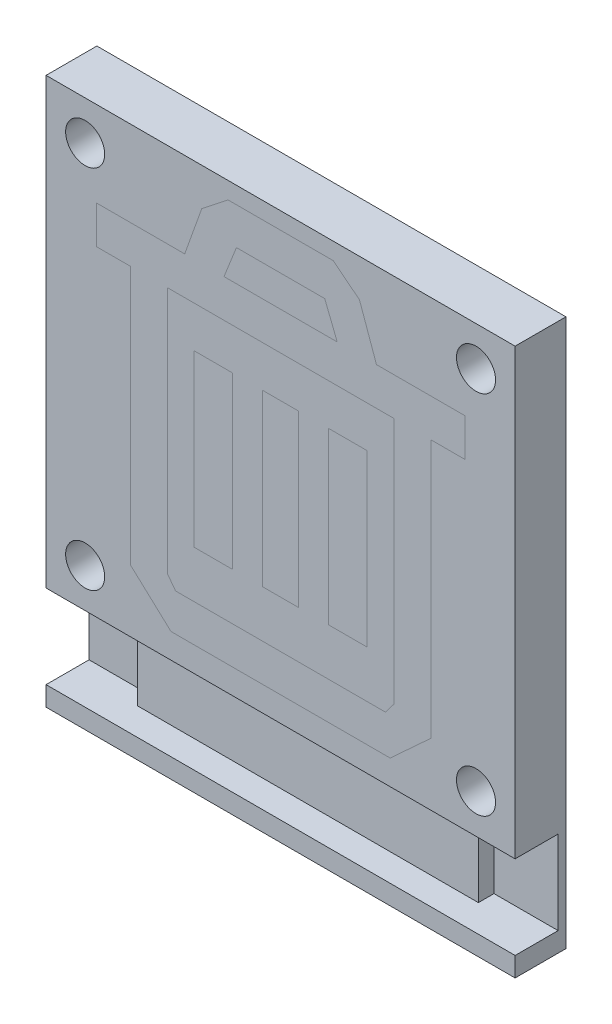
SolidWorks part; units mm, degrees
ref_plane "Front Plane" through (0, 0, 0) normal (0, 0, 1) x (1, 0, 0)
ref_plane "Top Plane" through (0, 0, 0) normal (0, 1, 0) x (1, 0, 0)
ref_plane "Right Plane" through (0, 0, 0) normal (1, 0, 0) x (0, 0, -1)
sketch "Sketch1" plane through (0, 0, 0) normal (0, 0, 1) x (1, 0, 0)
  line L0 (137.9686, 390.3403) -> (878.5926, 390.3403) construction
  line L1 (-39.205, 61.8798) -> (20.795, 61.8798)
  line L2 (-39.205, 61.8798) -> (-39.205, -8.1202)
  line L3 (-39.205, -8.1202) -> (20.795, -8.1202)
  line L4 (20.795, 61.8798) -> (20.795, -8.1202)
  line L5 (-9.205, -8.1202) -> (-9.205, 61.8798) construction
  line L6 (-9.205, 5.0798) -> (-9.205, -5.6202) construction
  line L7 (16.595, 5.0798) -> (-35.005, 5.0798)
  line L8 (16.595, 5.0798) -> (16.595, -5.6202)
  line L9 (16.595, -5.6202) -> (-35.005, -5.6202)
  line L10 (-35.005, 5.0798) -> (-35.005, -5.6202)
  line L11 (-2.4787, 59.7179) -> (-15.9313, 59.7179)
  line L12 (-35.005, -5.6202) -> (-31.005, -5.6202)
  line L13 (-35.005, -5.6202) -> (-35.005, 5.0798)
  line L14 (-35.005, 5.0798) -> (-31.005, 5.0798)
  line L15 (-31.005, -5.6202) -> (-31.005, 5.0798)
  line L16 (16.595, -5.6202) -> (12.595, -5.6202)
  line L17 (16.595, -5.6202) -> (16.595, 5.0798)
  line L18 (16.595, 5.0798) -> (12.595, 5.0798)
  line L19 (12.595, -5.6202) -> (12.595, 5.0798)
  line L20 (-35.005, 5.0798) -> (-39.205, 5.0798)
  line L21 (-35.005, 5.0798) -> (-35.005, -5.6202)
  line L22 (-35.005, -5.6202) -> (-39.205, -5.6202)
  line L23 (-39.205, 5.0798) -> (-39.205, -5.6202)
  line L24 (16.595, 5.0798) -> (20.795, 5.0798)
  line L25 (16.595, 5.0798) -> (16.595, -5.6202)
  line L26 (16.595, -5.6202) -> (20.795, -5.6202)
  line L27 (20.795, 5.0798) -> (20.795, -5.6202)
  line L28 (-15.9313, 59.7179) -> (-19.2931, 57.063)
  line L29 (-19.2931, 57.063) -> (-21.4699, 50.9645)
  line L30 (-21.4699, 50.9645) -> (-32.7735, 50.9645)
  line L31 (-32.7735, 50.9645) -> (-32.7735, 46.12)
  line L32 (-32.7735, 46.12) -> (-28.4218, 46.12)
  line L33 (-28.4218, 46.12) -> (-28.4218, 13.0402)
  line L34 (-28.4218, 13.0402) -> (-23.2226, 8.2562)
  line L35 (-23.2226, 8.2562) -> (4.8126, 8.2562)
  line L36 (4.2315, 13.0402) -> (-22.6415, 13.0402)
  line L37 (-22.6415, 13.0402) -> (-23.6864, 14.4507)
  line L38 (-23.6864, 14.4507) -> (-23.6864, 46.12)
  line L39 (-23.6864, 46.12) -> (5.2763, 46.12)
  line L40 (-1.9643, 50.9645) -> (-16.4457, 50.9645)
  line L41 (-16.4457, 50.9645) -> (-14.8536, 54.9715)
  line L42 (-14.8536, 54.9715) -> (-3.5564, 54.9715)
  line L43 (-6.911, 40.837) -> (-11.499, 40.837)
  line L44 (-11.499, 40.837) -> (-11.499, 19.0717)
  line L45 (-11.499, 19.0717) -> (-6.911, 19.0717)
  line L46 (-20.278, 40.837) -> (-15.3428, 40.837)
  line L47 (-15.3428, 40.837) -> (-15.3428, 19.0717)
  line L48 (-15.3428, 19.0717) -> (-20.278, 19.0717)
  line L49 (-20.278, 19.0717) -> (-20.278, 40.837)
  line L50 (1.868, 19.0717) -> (1.868, 40.837)
  line L51 (-3.0672, 19.0717) -> (1.868, 19.0717)
  line L52 (-3.0672, 40.837) -> (-3.0672, 19.0717)
  line L53 (1.868, 40.837) -> (-3.0672, 40.837)
  line L54 (-6.911, 40.837) -> (-6.911, 19.0717)
  line L55 (-1.9643, 50.9645) -> (-3.5564, 54.9715)
  line L56 (5.2763, 14.4507) -> (5.2763, 46.12)
  line L57 (4.2315, 13.0402) -> (5.2763, 14.4507)
  line L58 (10.0118, 13.0402) -> (4.8126, 8.2562)
  line L59 (10.0118, 46.12) -> (10.0118, 13.0402)
  line L60 (14.3635, 46.12) -> (10.0118, 46.12)
  line L61 (14.3635, 50.9645) -> (14.3635, 46.12)
  line L62 (3.0599, 50.9645) -> (14.3635, 50.9645)
  line L63 (0.8831, 57.063) -> (3.0599, 50.9645)
  line L64 (-2.4787, 59.7179) -> (0.8831, 57.063)
  point P34 (-9.205, 59.7179)
  point P35 (-9.205, 54.9715)
  point P36 (-9.205, 50.9645)
  point P37 (-9.205, 40.837)
  point P38 (-9.205, 46.12)
  point P39 (-9.205, 19.0717)
  point P40 (-9.205, 8.2562)
  point P41 (-9.205, 13.0402)
  dimension "D1" = 70
  dimension "D2" = 60
  dimension "D3" = 10.7
  dimension "D5" = 2.5
  dimension "D6" = 4
  dimension "D7" = 4
extrude "Back Plate" add sketch "Sketch1" along normal blind 1 contours L7 L24 L4 L1 L2 L20 | L9 L19 L7 L15 | L9 L15 L7 L10 | L22 L10 L20 L2 | L26 L9 L22 L2 L3 L4 | L19 L9 L8 L7 | L8 L26 L4 L24 | L36 L57 L56 L39 L38 L37 L43 L54 L45 L44 L48 L49 L46 L47 L53 L50 L51 L52 | L40 L55 L42 L41 region at (-9.205, 61.0536, 0) region at (-37.105, -0.2702, 0) region at (18.695, -0.2702, 0) region at (-9.205, -6.8702, 0) region at (-33.005, -0.2702, 0) region at (14.595, -0.2702, 0) region at (-9.205, -0.2702, 0) region at (-9.205, 13.4799, 0) region at (-9.205, 52.8855, 0)
extrude "Neopixel Back" add sketch "Sketch1<4>" along normal blind 3 contours L9 L19 L7 L15 region at (-9.205, -0.2702, 0)
sketch "Sketch1<4>" plane through (0, 0, 0) normal (0, 0, 1) x (1, 0, 0) same geometry as "Sketch1"
extrude "Main Color" add sketch "Sketch1<5>" along normal blind 6.5 contours L7 L24 L4 L1 L2 L20 | L26 L9 L22 L2 L3 L4 | L36 L57 L56 L39 L38 L37 L43 L54 L45 L44 L48 L49 L46 L47 L53 L50 L51 L52 | L40 L55 L42 L41 region at (-9.205, 61.0536, 0) region at (-9.205, -6.8702, 0) region at (-9.205, 13.4799, 0) region at (-9.205, 52.8855, 0)
sketch "Sketch1<5>" plane through (0, 0, 0) normal (0, 0, 1) x (1, 0, 0) same geometry as "Sketch1"
sketch "Sketch2" plane through (0, 0, 6.5) normal (0, 0, 1) x (1, 0, 0)
  line L0 (-9.205, 61.8798) -> (-9.205, 5.0798) construction
  line L1 (-39.205, 61.8798) -> (20.795, 61.8798) construction
  line L2 (20.795, 5.0798) -> (-39.205, 5.0798) construction
  line L3 (-39.205, 33.4798) -> (20.795, 33.4798) construction
  line L4 (-39.205, 61.8798) -> (-39.205, 5.0798) construction
  line L5 (20.795, 61.8798) -> (20.795, 5.0798) construction
  circle A0 centre (-34.205, 56.8798) radius 2.5
  circle A1 centre (15.795, 56.8798) radius 2.5
  circle A2 centre (-34.205, 10.0798) radius 2.5
  circle A3 centre (15.795, 10.0798) radius 2.5
  dimension "D1" = 5
  dimension "D2" = 5
  dimension "D3" = 5
extrude "Mounting Holes" cut sketch "Sketch2" against normal blind 6.5
extrude "Highlight Color" add sketch "Sketch1<7>" along normal blind 6.5 separate body contours L64 L11 L28 L29 L30 L31 L32 L33 L34 L35 L58 L59 L60 L61 L62 L63 L57 L36 L37 L38 L39 L56 L55 L40 L41 L42 | L49 L48 L47 L46 | L54 L43 L44 L45 | L50 L53 L52 L51 region at (-1.2303, 57.8428, 0) region at (-9.205, 29.9543, 0) region at (-17.8104, 29.9543, 0) region at (-0.5996, 29.9543, 0)
sketch "Sketch1<7>" plane through (0, 0, 0) normal (0, 0, 1) x (1, 0, 0) same geometry as "Sketch1"
